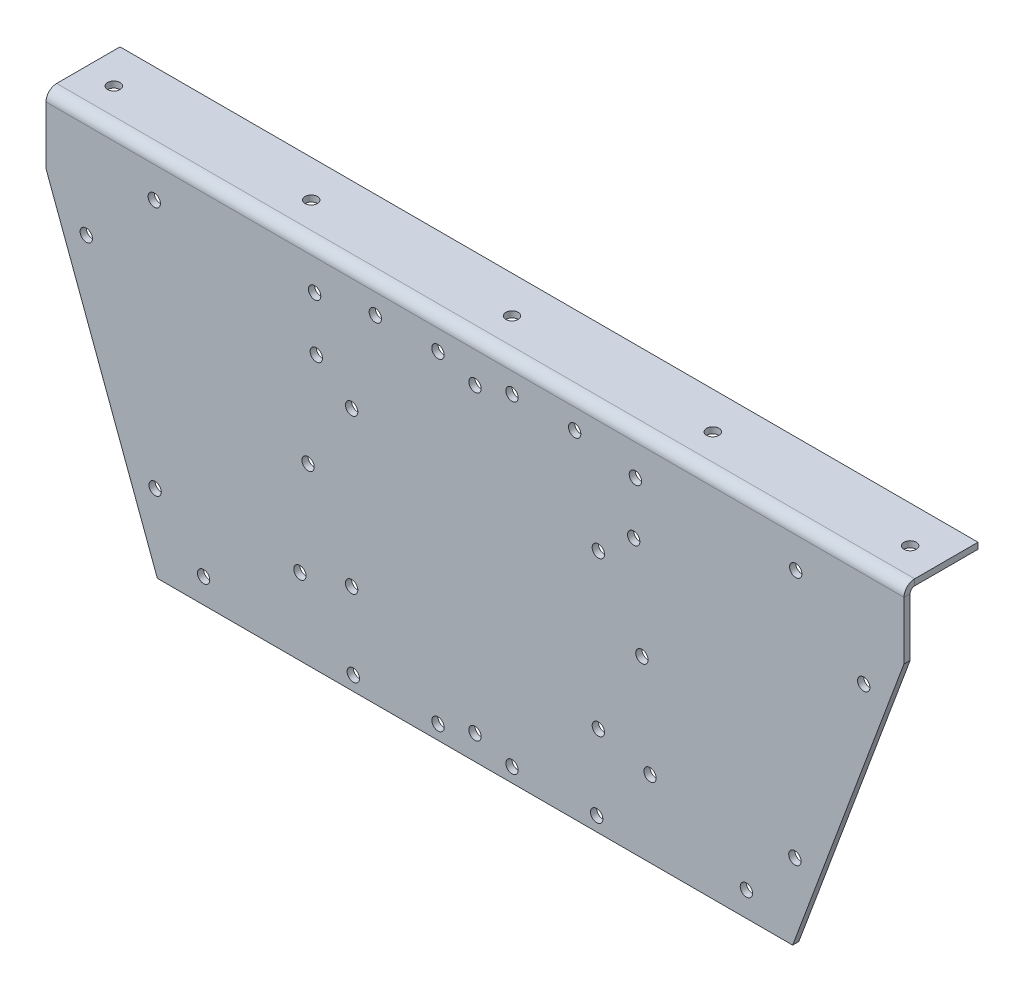
SolidWorks part; units mm, degrees
note: The reader was unsure of these and kept them because the rebuilt part matched: flange length of "邊線-凸緣1".
ref_plane "前基準面" through (0, 0, 0) normal (0, 0, 1) x (1, 0, 0)
ref_plane "上基準面" through (0, 0, 0) normal (0, 1, 0) x (1, 0, 0)
ref_plane "右基準面" through (0, 0, 0) normal (1, 0, 0) x (0, 0, -1)
sketch "草圖1" plane through (0, 0, 0) normal (0, 0, 1) x (1, 0, 0)
  line L0 (-69.55, 38.6) -> (69.55, 38.6)
  line L1 (69.55, 38.6) -> (69.55, 28.5)
  line L2 (69.55, 28.5) -> (51.5, -20)
  line L3 (51.5, -20) -> (-51.5, -20)
  line L4 (-51.5, -20) -> (-69.55, 28.5)
  line L5 (-69.55, 28.5) -> (-69.55, 38.6)
  dimension "D1" = 10.1
  dimension "D2" = 10.1
  dimension "D3" = 58.6
  dimension "D4" = 139.1
  dimension "D5" = 69.55
  dimension "D6" = 103
  dimension "D7" = 51.5
  dimension "D8" = 20
sheet metal parameters "鈑金1" thickness 1 parameters "D1"=0.7366
base flange "基材-凸緣1" sketch "草圖1" thickness 1 reverse thickness direction no parameters "D1"=0.7366
edge flange "邊線-凸緣1" sketch "草圖6" flange angle 90 flange length 11 flange position material outside bend radius 0.7366 thickness 1 relief rectangular parameters "D6"=10
sketch "草圖6" plane through (0, 38.6, -1) normal (0, 1, 0) x (1, 0, 0)
  line L0 (69.55, 0) -> (-69.55, 0) construction
  line L1 (69.55, 0) -> (-69.55, 0)
  line L2 (-69.55, 0) -> (-69.55, 11)
  line L3 (-69.55, 11) -> (69.55, 11)
  line L4 (69.55, 11) -> (69.55, 0)
bend "邊線彎折1" bend radius 0.7366 bend angle 90 parameters "D5"=1
sketch "草圖7" plane through (0, 0, 0) normal (0, 0, 1) x (1, 0, 0)
  line L0 (-66.9059, 32.8634) -> (-48.7206, -16) construction
  line L1 (-48.7206, -16) -> (48.7206, -16) construction
  line L2 (48.7206, -16) -> (66.9059, 32.8634) construction
  line L3 (66.9059, 32.8634) -> (-66.9059, 32.8634) construction
  line L4 (-69.55, 28.5) -> (-51.5, -20) construction
  line L5 (51.5, -20) -> (69.55, 28.5) construction
  line L6 (69.55, 37.8634) -> (-69.55, 37.8634) construction
  line L7 (-51.5, -20) -> (51.5, -20) construction
  circle A0 centre (0, 32.8634) radius 1
  circle A1 centre (0, -16) radius 1
  circle A2 centre (52, 32.8634) radius 1
  circle A3 centre (26, 32.8634) radius 1
  circle A4 centre (-52, 32.8634) radius 1
  circle A5 centre (-26, 32.8634) radius 1
  circle A6 centre (-63.0211, 22.4252) radius 1
  circle A7 centre (-51.8598, -7.5652) radius 1
  circle A8 centre (51.8598, -7.5652) radius 1
  circle A9 centre (63.0211, 22.4252) radius 1
  circle A10 centre (44, -16) radius 1
  circle A11 centre (-44, -16) radius 1
  dimension "D15" = 2
  dimension "D1" = 4
  dimension "D2" = 4
  dimension "D3" = 4
  dimension "D4" = 5
  dimension "D5" = 26
  dimension "D6" = 26
  dimension "D7" = 26
  dimension "D8" = 26
  dimension "D9" = 32
  dimension "D10" = 32
  dimension "D11" = 9
  dimension "D12" = 9
  dimension "D13" = 44
  dimension "D14" = 44
extrude "除料-伸長1" cut sketch "草圖7" against normal blind 2 normal cut yes
sketch "草圖8" plane through (0, 39.6, 0) normal (0, 1, 0) x (1, 0, 0)
  line L0 (-69.55, 6) -> (69.55, 6) construction
  line L1 (-69.55, 12) -> (-69.55, 1.7366) construction
  line L2 (69.55, 1.7366) -> (69.55, 12) construction
  line L3 (69.55, 12) -> (-69.55, 12) construction
  circle A0 centre (0, 6) radius 1
  circle A1 centre (64.55, 6) radius 1
  circle A2 centre (-64.55, 6) radius 1
  circle A3 centre (-32.55, 6) radius 1
  circle A4 centre (32.55, 6) radius 1
  dimension "D5" = 2
  dimension "D1" = 5
  dimension "D2" = 32
  dimension "D3" = 5
  dimension "D4" = 32
  dimension "D6" = 6
extrude "除料-伸長2" cut sketch "草圖8" against normal blind 2 normal cut yes
sketch "草圖9" plane through (0, 0, 0) normal (0, 0, 1) x (1, 0, 0)
  line L0 (0, 56.5158) -> (0, -33.0323) construction
  line L2 (69.55, 39.6) -> (-69.55, 39.6) construction
  circle A0 centre (-6, 34.6) radius 1
  circle A1 centre (-16.16, 34.6) radius 1
  circle A2 centre (16.16, 34.6) radius 1
  circle A3 centre (6, 34.6) radius 1
  dimension "D1" = 2
  dimension "D2" = 2
  dimension "D3" = 6
  dimension "D4" = 16.16
  dimension "D5" = 5
  dimension "D6" = 5
extrude "除料-伸長3" cut sketch "草圖9" against normal blind 10 normal cut yes
sketch "草圖10" plane through (0, 0, 0) normal (0, 0, 1) x (1, 0, 0)
  line L0 (0, 39.6) -> (0, -20) construction
  line L1 (69.55, 39.6) -> (-69.55, 39.6) construction
  line L2 (-51.5, -20) -> (51.5, -20) construction
  circle A0 centre (-20, 19.6) radius 1
  circle A1 centre (20, 19.6) radius 1
  circle A2 centre (20, -5.4) radius 1
  circle A3 centre (-20, -5.4) radius 1
  dimension "D1" = 2
  dimension "D2" = 2
  dimension "D3" = 2
  dimension "D4" = 2
  dimension "D5" = 20
  dimension "D6" = 20
  dimension "D7" = 20
  dimension "D8" = 20
  dimension "D9" = 20
  dimension "D10" = 20
  dimension "D11" = 25
  dimension "D12" = 25
extrude "除料-伸長4" cut sketch "草圖10" against normal blind 10 normal cut yes
sketch "草圖11" plane through (0, 0, 0) normal (0, 0, 1) x (1, 0, 0)
  line L0 (0, 48.8716) -> (0, -32.0215) construction
  line L1 (-51.5, -20) -> (51.5, -20) construction
  circle A0 centre (19.73, -17.69) radius 1
  circle A1 centre (6, -17.69) radius 1
  circle A3 centre (-19.73, -17.69) radius 1
  circle A4 centre (-6, -17.69) radius 1
  point P9 (8.6889, -19.4971)
  dimension "D1" = 2
  dimension "D2" = 2
  dimension "D3" = 6
  dimension "D4" = 2.31
  dimension "D5" = 2.31
  dimension "D6" = 19.73
extrude "除料-伸長5" cut sketch "草圖11" against normal through all normal cut yes
sketch "草圖12" plane through (0, 0, 0) normal (0, 0, 1) x (1, 0, 0)
  line L0 (0, 48.1841) -> (0, -44.3961) construction
  line L1 (-51.5, -20) -> (51.5, -20) construction
  circle A0 centre (25.73, 24.27) radius 1
  circle A1 centre (27.06, 8.32) radius 1
  circle A2 centre (28.38, -7.62) radius 1
  dimension "D1" = 2
  dimension "D2" = 2
  dimension "D3" = 2
  dimension "D4" = 44.27
  dimension "D5" = 28.32
  dimension "D6" = 12.38
  dimension "D7" = 25.73
  dimension "D8" = 27.06
  dimension "D9" = 28.38
extrude "除料-伸長6" cut sketch "草圖12" against normal blind 10 normal cut yes
mirror "鏡射1" about plane through (0, 0, 0) normal (1, 0, 0) of "除料-伸長6"
flat pattern "平板-型式1" [suppressed]
sketch "彎折-線1" plane through (0, 0, 0) normal (0, 1, 0) x (1, 0, 0)
sketch3d "邊界方塊1" [suppressed]
  line L0 (69.55, -20, 0) -> (-69.55, -20, 0) construction
  line L1 (69.55, 38.6, 0) -> (-69.55, 38.6, 0) construction
  line L2 (69.55, -20, 0) -> (69.55, 38.6, 0) construction
  line L3 (-69.55, -20, 0) -> (-69.55, 38.6, 0) construction
bend of the flat pattern "平板-<邊線彎折1>1"
